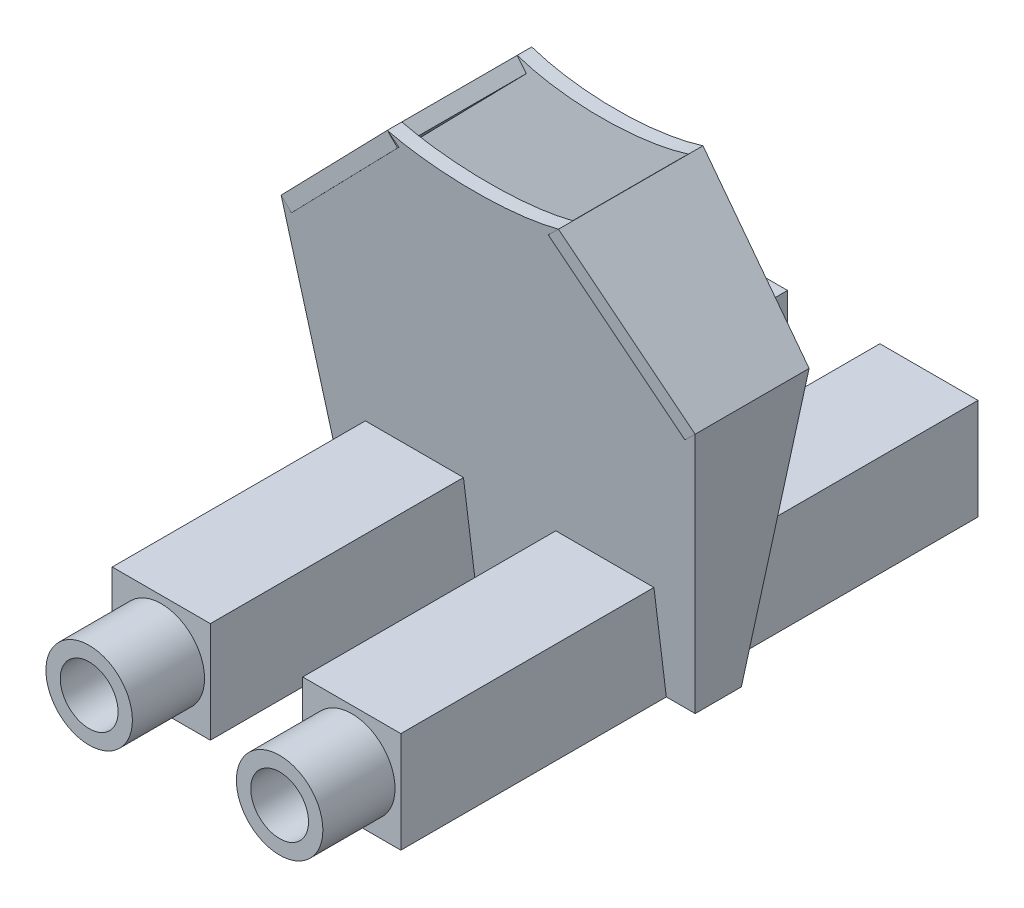
SolidWorks part; units mm, degrees
ref_plane "Front" through (0, 0, 0) normal (0, 0, 1) x (1, 0, 0)
ref_plane "Top" through (0, 0, 0) normal (0, 1, 0) x (1, 0, 0)
ref_plane "Right" through (0, 0, 0) normal (1, 0, 0) x (0, 0, -1)
sketch "Sketch1" plane through (0, 0, 0) normal (0, 1, 0) x (1, 0, 0)
  line L1 (-6, 0.8) -> (6, 0.8)
  line L2 (-6, 0.8) -> (-6, -0.8)
  line L3 (-6, -0.8) -> (6, -0.8)
  line L4 (6, 0.8) -> (6, -0.8)
  line L5 (-6, 0.8) -> (6, -0.8) construction
  line L6 (-6, -0.8) -> (6, 0.8) construction
  point P0 (0, 0)
  dimension "D1" = 1.6
  dimension "D2" = 12
extrude "Boss-Extrude1" add sketch "Sketch1" along normal blind 15 draft 7 draft outward yes
shell "Shell1" thickness 0.5 removed face at (0, 15, 0)
sketch "Sketch6" plane through (0, 0, 0) normal (0, -1, 0) x (1, 0, 0)
  line L1 (-1.6, -10) -> (-5, -10)
  line L2 (-1.6, -10) -> (-1.6, 10)
  line L3 (-1.6, 10) -> (-5, 10)
  line L4 (-5, -10) -> (-5, 10)
  line L5 (-1.6, -10) -> (-5, 10) construction
  line L6 (-1.6, 10) -> (-5, -10) construction
  line L7 (1.6, 10) -> (5, 10)
  line L8 (1.6, 10) -> (1.6, -10)
  line L9 (1.6, -10) -> (5, -10)
  line L10 (5, 10) -> (5, -10)
  line L11 (1.6, 10) -> (5, -10) construction
  line L12 (1.6, -10) -> (5, 10) construction
  point P0 (-3.3, 0)
  point P5 (3.3, 0)
  dimension "D1" = 3.4
  dimension "D2" = 20
  dimension "D3" = 3.4
extrude "Boss-Extrude2" add sketch "Sketch6" against normal blind 3.5 separate body
sketch "Sketch11" plane through (0, 0, 0) normal (0, 0, 1) x (1, 0, 0)
  line L1 (-7.8418, 15) -> (7.8418, 15) construction
  ellipse E0 centre (0, 15) end of major axis (4.5, 15) minor radius 1.5
extrude "Cut-Extrude11" cut sketch "Sketch11" against normal blind 10 and the other way blind 10
sketch "Sketch18" plane through (0, 0, 0) normal (0, 0, 1) x (1, 0, 0)
  line L0 (-2.9665, 13.8721) -> (-7.1737, 9.559)
  line L1 (-7.8418, 15) -> (-6, 0) construction
  line L2 (-7.1737, 9.559) -> (-8.985, 15.8134)
  line L3 (-8.985, 15.8134) -> (-2.9665, 15.8134)
  line L4 (-2.9665, 15.8134) -> (-2.9665, 13.8721)
extrude "Cut-Extrude12" cut sketch "Sketch18" against normal blind 10 and the other way blind 10
sketch "Sketch19" plane through (-8.454, 8.2465, 0) normal (-0.7158, 0.6983, 0) x (0, 0, 1)
  line L0 (1.9737, 1.8336) -> (2.5033, 7.8588)
  line L1 (2.5033, 7.8588) -> (-2.5033, 7.8588)
  line L2 (1.9737, 1.8336) -> (-1.9737, 1.8336)
  line L3 (-1.9737, 1.8336) -> (-2.5033, 7.8588)
extrude "Boss-Extrude3" add sketch "Sketch19" against normal blind 0.5
mirror "Mirror3" about plane through (0, 0, 0) normal (1, 0, 0) of "Boss-Extrude3"
sketch "Sketch20" plane through (0, 0, 10) normal (0, 0, 1) x (1, 0, 0)
  circle A0 centre (3.3, 1.75) radius 1.4991
  dimension "D1" = 2.9982
extrude "Boss-Extrude4" add sketch "Sketch20" along normal blind 2.5
sketch "Sketch22" plane through (0, 0, 12.5) normal (0, 0, 1) x (1, 0, 0)
  circle A0 centre (3.3, 1.75) radius 1.0014
  dimension "D1" = 2.0028
extrude "Cut-Extrude13" cut sketch "Sketch22" against normal blind 15
sketch "Sketch25" plane through (0, 3.5, 0) normal (0, 1, 0) x (1, 0, 0)
  line L1 (-4.372, 0.7261) -> (-2.372, 0.7261)
  line L2 (-4.372, 0.7261) -> (-4.372, -0.6739)
  line L3 (-4.372, -0.6739) -> (-2.372, -0.6739)
  line L4 (-2.372, 0.7261) -> (-2.372, -0.6739)
  line L5 (-4.372, 0.7261) -> (-2.372, -0.6739) construction
  line L6 (-4.372, -0.6739) -> (-2.372, 0.7261) construction
  point P0 (-3.372, 0.0261)
  dimension "D1" = 2
  dimension "D2" = 1.4
extrude "Cut-Extrude14" cut sketch "Sketch25" against normal blind 1.5
mirror "Mirror6" about plane through (0, 0, 0) normal (1, 0, 0) of "Cut-Extrude14"
sketch "Sketch28" plane through (0, 0, 10) normal (0, 0, 1) x (1, 0, 0)
  circle A0 centre (-3.3, 1.75) radius 1.4984
  dimension "D1" = 2.9967
extrude "Boss-Extrude5" add sketch "Sketch28" along normal blind 2.5
sketch "Sketch29" plane through (0, 0, 12.5) normal (0, 0, 1) x (1, 0, 0)
  circle A0 centre (-3.3, 1.75) radius 1.0022
  dimension "D1" = 2.0043
extrude "Cut-Extrude15" cut sketch "Sketch29" against normal blind 15
sketch "Sketch30" plane through (0, 0, 0) normal (0, -1, 0) x (1, 0, 0)
  line L0 (1.6, 10) -> (1.6, -10) construction
  line L1 (-1.6, 0.8) -> (1.6, 0.8)
  line L2 (-1.6, 0.8) -> (-1.6, -0.8)
  line L3 (-1.6, -0.8) -> (1.6, -0.8)
  line L4 (1.6, 0.8) -> (1.6, -0.8)
  line L5 (-1.6, 0.8) -> (1.6, -0.8) construction
  line L6 (-1.6, -0.8) -> (1.6, 0.8) construction
  line L7 (6, -0.8) -> (-6, -0.8) construction
  point P0 (0, 0)
extrude "Boss-Extrude6" add sketch "Sketch30" against normal blind 9 draft 6 draft outward yes
mirror "Mirror7" about plane through (0, 0, 0) normal (1, 0, 0) of "Cut-Extrude12"
